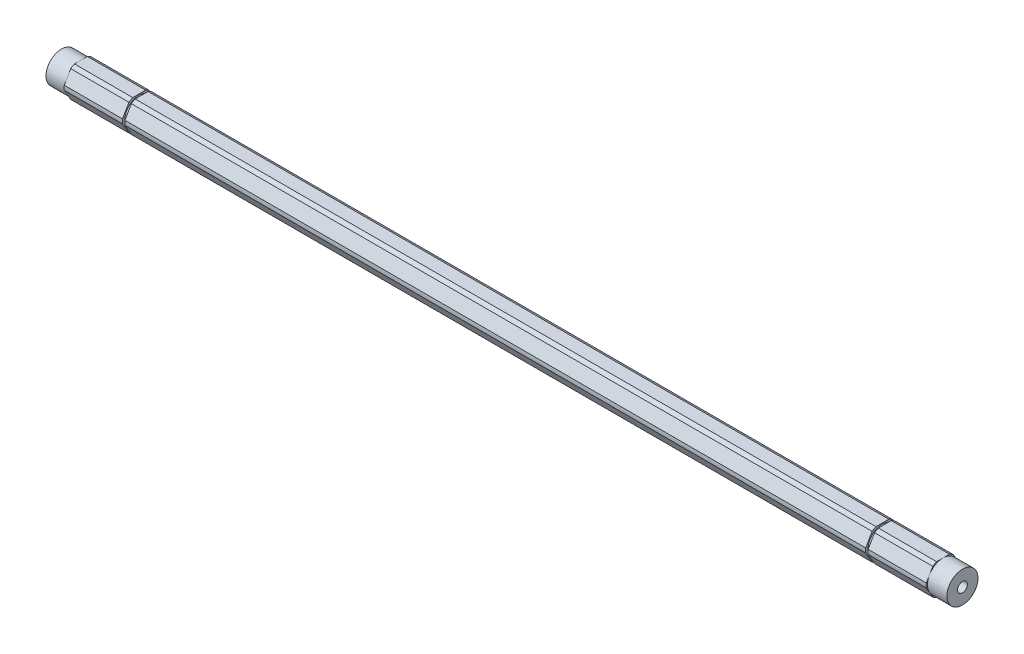
SolidWorks part; units mm, degrees
material "7075-T6 (SN)"
ref_plane "Front Plane" through (0, 0, 0) normal (0, 0, 1) x (1, 0, 0)
ref_plane "Top Plane" through (0, 0, 0) normal (0, 1, 0) x (1, 0, 0)
ref_plane "Right Plane" through (0, 0, 0) normal (1, 0, 0) x (0, 0, -1)
sketch "Sketch1" plane through (0, 0, 0) normal (1, 0, 0) x (0, 0, -1)
  line L1 (7.3323, 0) -> (3.6662, 6.35)
  line L2 (3.6662, 6.35) -> (-3.6662, 6.35)
  line L3 (-3.6662, 6.35) -> (-7.3323, 0)
  line L4 (-7.3323, 0) -> (-3.6662, -6.35)
  line L5 (-3.6662, -6.35) -> (3.6662, -6.35)
  line L6 (3.6662, -6.35) -> (7.3323, 0)
  circle A0 centre (0, 0) radius 6.875
  circle A1 centre (0, 0) radius 2.0193
  circle A2 centre (0, 0) radius 6.35 construction
  dimension "D1" = 12.7
  dimension "D2" = 13.75
  dimension "D3" = 4.0386
extrude "Boss-Extrude1" add sketch "Sketch1" along normal mid plane 368.3 contours L1 A0 L2 L3 L4 L5 L6 A1 region at (0, 0.4353, -6.6736)
sketch "Sketch2" plane through (184.15, 0, 0) normal (1, 0, 0) x (0, 0, -1)
  circle A0 centre (0, 0) radius 6.35
  dimension "D1" = 12.7
extrude "Cut-Extrude-Thin1" cut sketch "Sketch2" against normal blind 7.9375 thin thin type one direction wall 2.54
mirror "Mirror1" about plane through (0, 0, 0) normal (1, 0, 0) of "Cut-Extrude-Thin1"
sketch "Sketch4" plane through (0, 0, 0) normal (0, 0, 1) x (1, 0, 0)
  line L0 (184.15, -6.35) -> (184.15, 6.35) construction
  line L1 (151.4094, 8.6573) -> (152.4, 8.6573)
  line L2 (151.4094, 8.6573) -> (151.4094, 5.8547)
  line L3 (151.4094, 5.8547) -> (152.4, 5.8547)
  line L4 (152.4, 8.6573) -> (152.4, 5.8547)
  line L7 (176.2125, 0) -> (-176.2125, 0) construction
  dimension "D1" = 31.75
  dimension "D2" = 0.9906
  dimension "D3" = 5.8547
revolve "Cut-Revolve7" cut sketch "Sketch4" angle 360 about axis through (184.15, 0, 0) along (-1, 0, 0)
mirror "Mirror2" about plane through (0, 0, 0) normal (1, 0, 0) of "Cut-Revolve7"
equation "\"D2@Sketch1\"=13.75mm"
